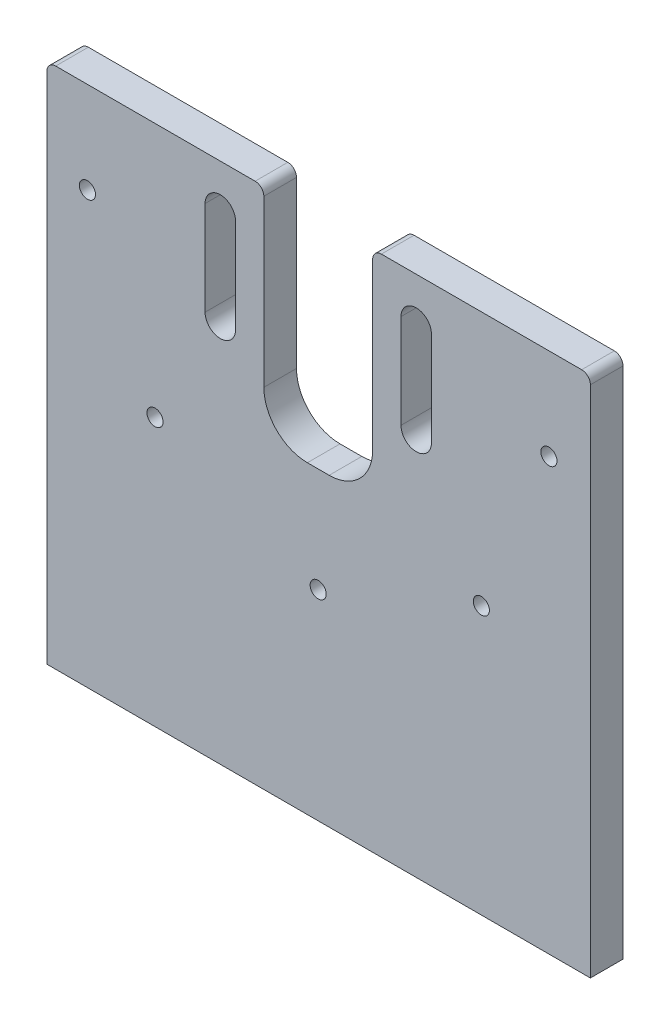
SolidWorks part; units mm, degrees
ref_plane "Front Plane" through (0, 0, 0) normal (0, 0, 1) x (1, 0, 0)
ref_plane "Top Plane" through (0, 0, 0) normal (0, 1, 0) x (1, 0, 0)
ref_plane "Right Plane" through (0, 0, 0) normal (1, 0, 0) x (0, 0, -1)
sketch "Sketch1" plane through (0, 0, 0) normal (0, 1, 0) x (1, 0, 0)
  line L8 (0, -7.5) -> (125, -7.5)
  line L10 (0, 157.5) -> (125, 157.5)
  line L12 (0, -7.5) -> (0, 0)
  line L14 (125, -7.5) -> (125, 0)
  line L15 (0, 157.5) -> (0, 150)
  line L16 (125, 157.5) -> (125, 150)
  line L17 (150, 54) -> (150, 96)
  line L18 (-30, 60) -> (-30, 90)
  line L19 (125, 150) -> (150, 96)
  line L20 (150, 54) -> (125, 0)
  line L21 (0, 0) -> (-30, 60)
  line L22 (-30, 90) -> (0, 150)
  line L23 (137.5, 55.5) -> (137.5, 94.5) construction
  line L24 (134.5, 55.5) -> (134.5, 94.5)
  line L25 (140.5, 55.5) -> (140.5, 94.5)
  line L26 (-14, 55.5) -> (-14, 94.5) construction
  line L27 (-17, 55.5) -> (-17, 94.5)
  line L28 (-11, 55.5) -> (-11, 94.5)
  line L29 (62.5, 11) -> (62.5, 50) construction
  line L30 (59.5, 11) -> (59.5, 50)
  line L31 (65.5, 11) -> (65.5, 50)
  line L32 (62.5, 138.7057) -> (62.5, 99.7057) construction
  line L33 (65.5, 138.7057) -> (65.5, 99.7057)
  line L34 (59.5, 138.7057) -> (59.5, 99.7057)
  arc A0 (134.5, 55.5) -> (140.5, 55.5) centre (137.5, 55.5) ccw
  arc A1 (140.5, 94.5) -> (134.5, 94.5) centre (137.5, 94.5) ccw
  arc A2 (-17, 55.5) -> (-11, 55.5) centre (-14, 55.5) ccw
  arc A3 (-11, 94.5) -> (-17, 94.5) centre (-14, 94.5) ccw
  arc A4 (59.5, 11) -> (65.5, 11) centre (62.5, 11) ccw
  arc A5 (65.5, 50) -> (59.5, 50) centre (62.5, 50) ccw
  arc A6 (65.5, 138.7057) -> (59.5, 138.7057) centre (62.5, 138.7057) ccw
  arc A7 (59.5, 99.7057) -> (65.5, 99.7057) centre (62.5, 99.7057) ccw
  point P18 (137.5, 75)
  point P23 (-14, 75)
  point P30 (62.5, 30.5)
  point P35 (62.5, 119.2057)
sketch "Sketch2" plane through (0, 0, 0) normal (0, 0, 1) x (1, 0, 0)
  line L1 (0, 0) -> (0, 118)
  line L9 (2, 120) -> (47.8128, 120)
  line L10 (49.8128, 118) -> (49.8128, 80)
  line L11 (59.8128, 70) -> (64.8128, 70)
  line L12 (74.8128, 80) -> (74.8128, 118)
  line L13 (76.8128, 120) -> (122.8128, 120)
  line L14 (124.8128, 118) -> (124.8128, 0)
  line L15 (0, 0) -> (124.8128, 0)
  line L16 (39.8128, 88.1904) -> (39.8128, 109.8096) construction
  line L17 (36.3128, 88.1904) -> (36.3128, 109.8096)
  line L18 (43.3128, 88.1904) -> (43.3128, 109.8096)
  line L20 (84.8128, 88.1904) -> (84.8128, 109.8096) construction
  line L21 (88.3128, 88.1904) -> (88.3128, 109.8096)
  line L22 (81.3128, 88.1904) -> (81.3128, 109.8096)
  arc A6 (59.8128, 70) -> (49.8128, 80) centre (59.8128, 80) cw
  arc A7 (64.8128, 70) -> (74.8128, 80) centre (64.8128, 80) ccw
  arc A8 (49.8128, 118) -> (47.8128, 120) centre (47.8128, 118) ccw
  arc A9 (76.8128, 120) -> (74.8128, 118) centre (76.8128, 118) ccw
  arc A10 (2, 120) -> (0, 118) centre (2, 118) ccw
  arc A11 (124.8128, 118) -> (122.8128, 120) centre (122.8128, 118) ccw
  arc A14 (36.3128, 88.1904) -> (43.3128, 88.1904) centre (39.8128, 88.1904) ccw
  arc A15 (43.3128, 109.8096) -> (36.3128, 109.8096) centre (39.8128, 109.8096) ccw
  arc A16 (88.3128, 88.1904) -> (81.3128, 88.1904) centre (84.8128, 88.1904) cw
  arc A17 (81.3128, 109.8096) -> (88.3128, 109.8096) centre (84.8128, 109.8096) cw
  circle A32 centre (115.2936, 99) radius 1.85
  circle A33 centre (99.7703, 61.5233) radius 1.85
  circle A34 centre (62.2936, 46) radius 1.85
  circle A36 centre (24.817, 61.5233) radius 1.85
  circle A53 centre (9.2936, 99) radius 1.85
  point P23 (49.8128, 99)
  point P24 (39.8128, 99)
  point P32 (84.8128, 99)
  point P117 (62.2936, 99)
  dimension "D3" = 2
  dimension "D4" = 2
  dimension "D5" = 2
  dimension "D6" = 2
extrude "Boss-Extrude7" add sketch "Sketch2" along normal blind 7.5
